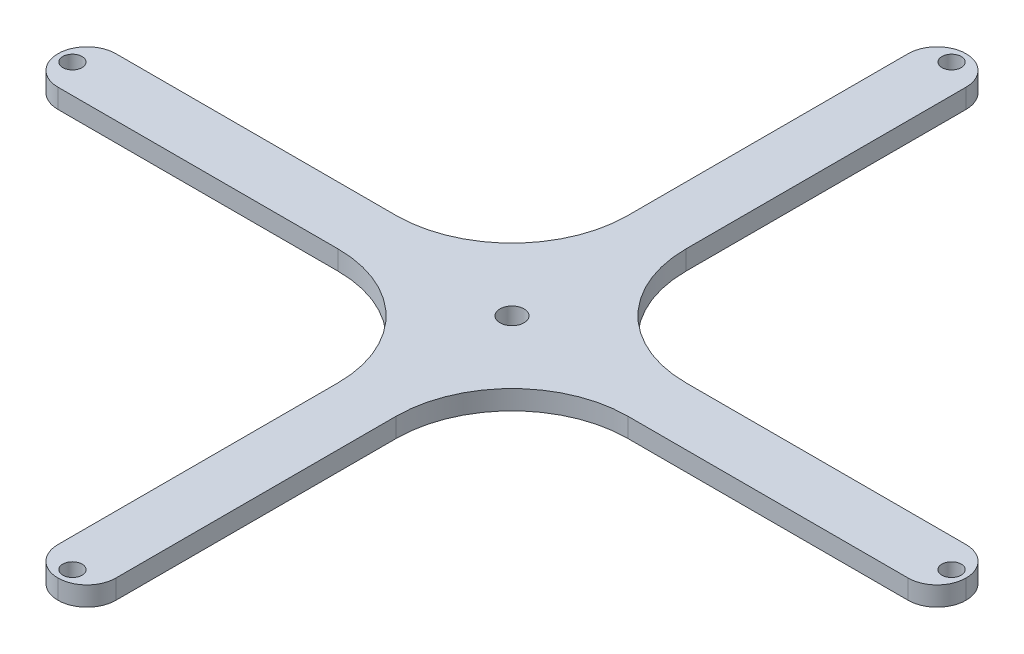
SolidWorks part; units mm, degrees
material "6061-T6 (SS)"
ref_plane "Front Plane" through (0, 0, 0) normal (0, 0, 1) x (1, 0, 0)
ref_plane "Top Plane" through (0, 0, 0) normal (0, 1, 0) x (1, 0, 0)
ref_plane "Right Plane" through (0, 0, 0) normal (1, 0, 0) x (0, 0, -1)
sketch "Sketch2" plane through (0, 0, 0) normal (0, 1, 0) x (1, 0, 0)
  line L0 (-148.9207, -9.525) -> (-9.525, -9.525)
  line L5 (-9.525, -148.9207) -> (-9.525, -9.525)
  line L7 (9.525, -148.9207) -> (9.525, -9.525)
  line L9 (-0.5237, -9.525) -> (0.5237, 9.525) construction
  line L10 (-0.5237, 9.525) -> (0.5237, -9.525) construction
  line L12 (-148.9207, 9.525) -> (-9.525, 9.525)
  line L13 (-9.525, 148.9207) -> (-9.525, 9.525)
  line L15 (9.525, 148.9207) -> (9.525, 9.525)
  line L16 (148.9207, 9.525) -> (9.525, 9.525)
  line L17 (148.9207, -9.525) -> (9.525, -9.525)
  line L18 (9.525, -9.525) -> (148.9207, -9.525)
  line L19 (0.5237, -9.525) -> (-0.5237, -9.525)
  line L20 (9.525, 9.525) -> (9.525, 148.9207)
  line L21 (9.525, -9.525) -> (9.525, -148.9207)
  line L27 (9.525, 9.525) -> (148.9207, 9.525)
  line L28 (0.5237, 9.525) -> (-0.5237, 9.525)
  line L29 (-0.5237, 9.525) -> (0.5237, 9.525)
  line L30 (-9.525, 9.525) -> (-148.9207, 9.525)
  line L31 (-9.525, 9.525) -> (-9.525, 148.9207)
  line L32 (-9.525, -9.525) -> (-9.525, -148.9207)
  line L33 (-0.5237, -9.525) -> (0.5237, -9.525)
  line L34 (-9.525, -9.525) -> (-148.9207, -9.525)
  circle A0 centre (0, 0) radius 3.9688
  circle A11 centre (144.4625, 0) radius 3.175
  circle A12 centre (0, -144.4625) radius 3.175
  circle A13 centre (0, 144.4625) radius 3.175
  circle A16 centre (0, 0) radius 149.225
  circle A17 centre (-144.4625, 0) radius 3.175
  point P30 (0, 0)
  point P34 (0, 0)
  point P35 (0, 0)
  point P38 (0, 0)
  dimension "D1" = 298.45
  dimension "D2" = 7.9375
  dimension "D3" = 6.35
  dimension "D4" = 4
extrude "Boss-Extrude1" add sketch "Sketch2" along normal blind 6.35 contours L17 A16 L16 L15 L13 L12 L0 L5 L7 A17 A0 A11 A12 A13 region at (-148.8029, 0, 0)
fillet "Fillet1" radius 9.525 8 edges at (-9.525, 3.175, -148.9207) (9.525, 3.175, -148.9207) (148.9207, 3.175, -9.525) (148.9207, 3.175, 9.525) (9.525, 3.175, 148.9207) (-9.525, 3.175, 148.9207) (-148.9207, 3.175, -9.525) (-148.9207, 3.175, 9.525)
fillet "Fillet3" radius 38.1 4 edges at (9.525, 3.175, 9.525) (-9.525, 3.175, 9.525) (-9.525, 3.175, -9.525) (9.525, 3.175, -9.525)
